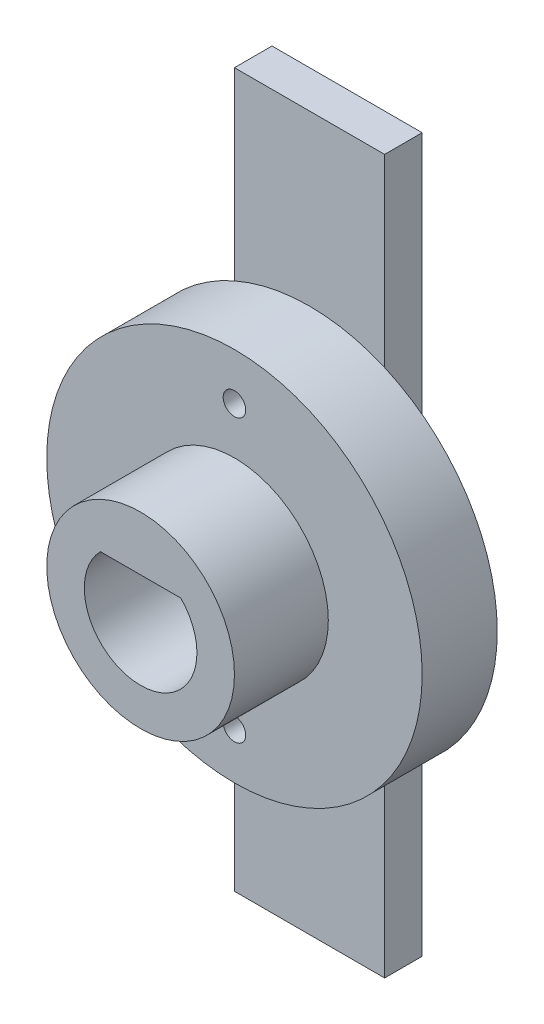
SolidWorks part; units mm, degrees
ref_plane "Plan de face" through (0, 0, 0) normal (0, 0, 1) x (1, 0, 0)
ref_plane "Plan de dessus" through (0, 0, 0) normal (0, 1, 0) x (1, 0, 0)
ref_plane "Plan de droite" through (0, 0, 0) normal (1, 0, 0) x (0, 0, -1)
sketch "Esquisse1" plane through (0, 0, 0) normal (0, 0, 1) x (1, 0, 0)
  line L8 (0, -7.5) -> (0, 7.5) construction
  circle A2 centre (0, -7.5) radius 0.6
  circle A3 centre (0, 7.5) radius 0.6
  circle A4 centre (0, 0) radius 10
  point P6 (0, 0)
  dimension "D2" = 1.2
  dimension "D3" = 1.2
  dimension "D4" = 20
  dimension "D1" = 15
extrude "Boss.-Extru.1" add sketch "Esquisse1" along normal blind 4
sketch "Esquisse2" [suppressed] plane through (0, 0, 10) normal (0, 0, 1) x (1, 0, 0)
  line L0 (-2.2, -2.0396) -> (-2.2, 2.0396)
  line L1 (3, -1.1913) -> (3, 1.3119) construction
  arc A0 (-2.2, -2.0396) -> (-2.2, 2.0396) centre (0, 0) ccw
  dimension "D1" = 6
  dimension "D2" = 5.2
extrude "Enlèv. mat.-Extru.1" [suppressed] cut sketch "Esquisse2" against normal offset from surface (8 mm away) 2 up to face at (10, 0, 0)
sketch "Esquisse3" plane through (0, 0, 4) normal (0, 0, 1) x (1, 0, 0)
  line L0 (-2.1424, 2.1) -> (2.1424, 2.1)
  line L1 (-0.8426, -3) -> (1.2459, -3) construction
  circle A0 centre (0, 0) radius 5
  arc A1 (-2.1424, 2.1) -> (2.1424, 2.1) centre (0, 0) ccw
  dimension "D1" = 6
  dimension "D3" = 10
  dimension "D2" = 5.1
extrude "Boss.-Extru.2" add sketch "Esquisse3" along normal blind 5
sketch "Esquisse4" plane through (0, 0, 0) normal (0, 0, -1) x (-1, 0, 0)
  line L1 (-4, 19) -> (4, 19)
  line L2 (-4, 19) -> (-4, -19)
  line L3 (-4, -19) -> (4, -19)
  line L4 (4, 19) -> (4, -19)
  point P4 (0, 19)
  point P5 (-4, 0)
  dimension "D1" = 8
  dimension "D2" = 38
extrude "Boss.-Extru.3" add sketch "Esquisse4" along normal blind 2
